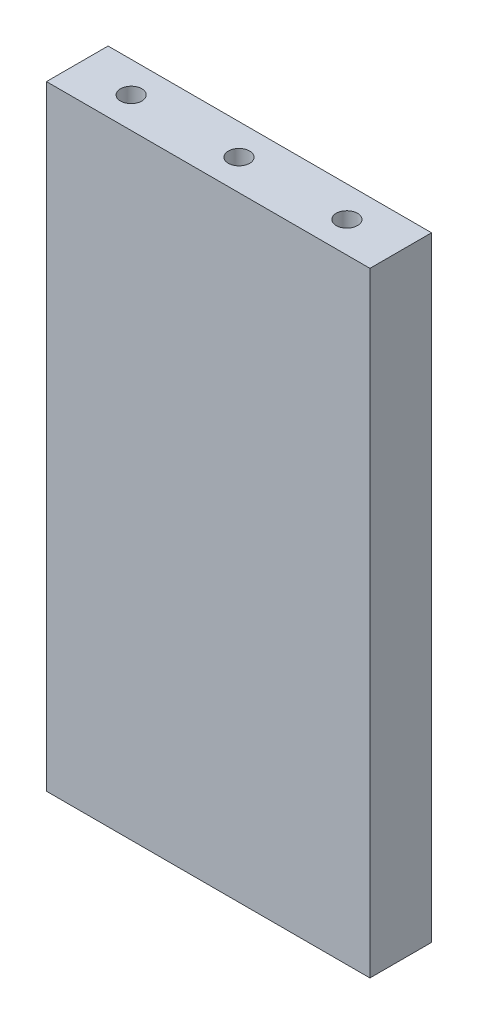
SolidWorks part; units mm, degrees
ref_plane "Front Plane" through (0, 0, 0) normal (0, 0, 1) x (1, 0, 0)
ref_plane "Top Plane" through (0, 0, 0) normal (0, 1, 0) x (1, 0, 0)
ref_plane "Right Plane" through (0, 0, 0) normal (1, 0, 0) x (0, 0, -1)
sketch "Sketch1" plane through (0, 0, 0) normal (0, 0, 1) x (1, 0, 0)
  line L1 (-25, -47.5) -> (25, -47.5)
  line L2 (-25, -47.5) -> (-25, 47.5)
  line L3 (-25, 47.5) -> (25, 47.5)
  line L4 (25, -47.5) -> (25, 47.5)
  line L5 (-25, -47.5) -> (25, 47.5) construction
  line L6 (-25, 47.5) -> (25, -47.5) construction
  point P0 (0, 0)
  dimension "D1" = 95
  dimension "D2" = 50
extrude "Boss-Extrude1" add sketch "Sketch1" against normal blind 9.525
sketch "Sketch2" plane through (0, 47.5, 0) normal (0, 1, 0) x (1, 0, 0)
  line L0 (25, 0) -> (-25, 0) construction
  point P0 (0, 4.7625)
  point P1 (16.67, 4.7625)
  point P2 (-16.67, 4.7625)
  dimension "D1" = 4.7625
  dimension "D2" = 16.67
  dimension "D3" = 16.67
sketch "Sketch3" plane through (0, -47.5, 0) normal (0, -1, 0) x (1, 0, 0)
  point P0 (16.67, -4.7625)
  point P2 (0, -4.7625)
  point P4 (-16.67, -4.7625)
hole_wizard "M4x0.7 Tapped Hole1" positions "Sketch3" profile "Sketch4" tap size "M4x0.7" standard "ANSI Metric"
sketch "Sketch4" plane through (16.67, -47.5, -4.7625) normal (1, 0, 0) x (0, 0, -1)
  line L0 (0, 0) -> (0, 10.9914)
  line L1 (0, 10.9914) -> (1.65, 10)
  line L2 (1.65, 10) -> (1.65, 0)
  line L5 (1.65, 0) -> (0, 0)
  line L10 (0, 10.9914) -> (-1.65, 10) construction
  line L11 (0, -6.35) -> (0, 107.95) construction
  dimension "Tap Drill Dia." = 3.3
  dimension "Tap Drill Depth" = 10
  dimension "Drill Angle" = 118
hole_wizard "M4x0.7 Tapped Hole2" positions "Sketch2" profile "Sketch5" tap size "M4x0.7" standard "ANSI Metric"
sketch "Sketch5" plane through (0, 47.5, -4.7625) normal (1, 0, 0) x (0, 0, 1)
  line L0 (0, 0) -> (0, 10.9914)
  line L1 (0, 10.9914) -> (1.65, 10)
  line L2 (1.65, 10) -> (1.65, 0)
  line L5 (1.65, 0) -> (0, 0)
  line L10 (0, 10.9914) -> (-1.65, 10) construction
  line L11 (0, -6.35) -> (0, 107.95) construction
  dimension "Tap Drill Dia." = 3.3
  dimension "Tap Drill Depth" = 10
  dimension "Drill Angle" = 118
